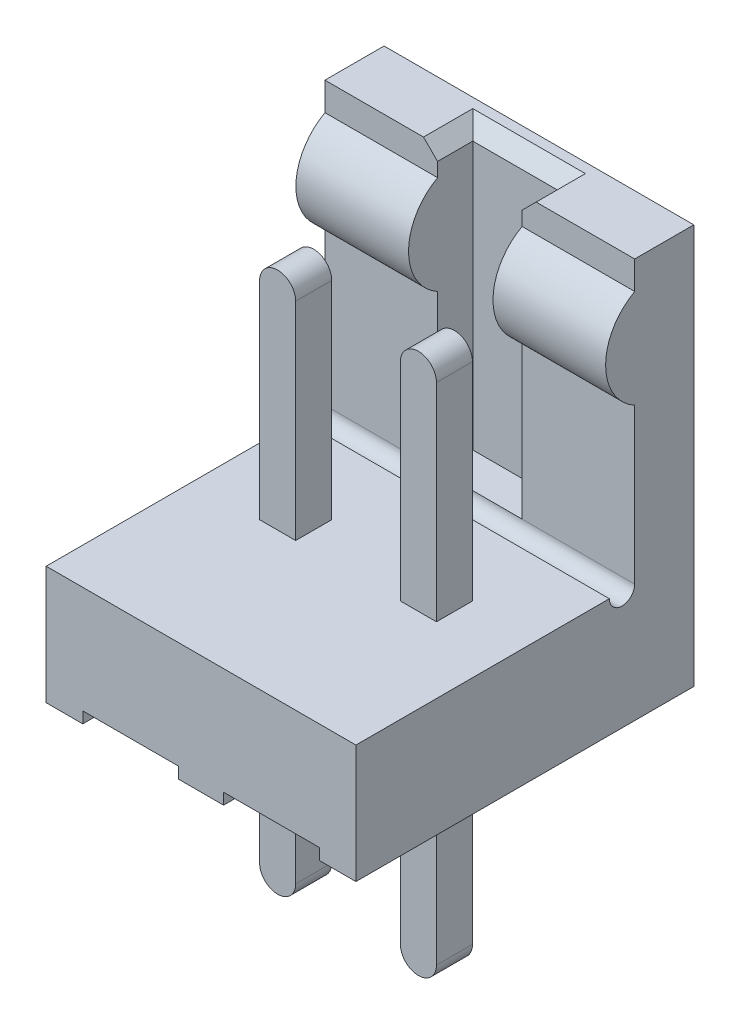
SolidWorks part; units mm, degrees
ref_plane "Front Plane" through (0, 0, 0) normal (0, 0, 1) x (1, 0, 0)
ref_plane "Top Plane" through (0, 0, 0) normal (0, 1, 0) x (1, 0, 0)
ref_plane "Right Plane" through (0, 0, 0) normal (1, 0, 0) x (0, 0, -1)
sketch "Sketch1" plane through (0, 0, 0) normal (1, 0, 0) x (0, 0, -1)
  line L0 (-3, 0) -> (3, 0)
  line L1 (3, 0) -> (3, 7.1)
  line L2 (3, 7.1) -> (1.95, 7.1)
  line L3 (1.95, 7.1) -> (1.95, 6.6)
  line L4 (-3, 0) -> (-3, 2.1)
  line L5 (-3, 2.1) -> (1.5, 2.1)
  line L6 (1.95, 2.1) -> (1.95, 4.85)
  arc A1 (1.95, 4.85) -> (1.95, 6.6) centre (2.4341, 5.725) cw
  arc A2 (1.95, 2.1) -> (1.5, 2.1) centre (1.725, 2.1) cw
  point P12 (0, 0)
  point P13 (1.95, 4.8078)
  dimension "D6" = 0.5
  dimension "D8" = 1
  dimension "D1" = 6
  dimension "D2" = 2.1
  dimension "D3" = 7.1
  dimension "D4" = 1.05
  dimension "D5" = 4.5
  dimension "D7" = 2.75
extrude "Boss-Extrude1" add sketch "Sketch1" along normal blind 2.75 and the other way blind 2.75
sketch "Sketch2" plane through (0, 2.1, 0) normal (0, 1, 0) x (1, 0, 0)
  line L0 (-2.75, 1.95) -> (2.75, 1.95)
  line L1 (-2.75, 1.95) -> (2.75, 1.95) construction
  line L3 (-0.75, 1.325) -> (0.75, 1.325)
  line L4 (-0.75, 1.325) -> (-0.75, 2.575)
  line L5 (-0.75, 2.575) -> (0.75, 2.575)
  line L6 (0.75, 1.325) -> (0.75, 2.575)
  line L7 (-0.75, 1.325) -> (0.75, 2.575) construction
  line L8 (-0.75, 2.575) -> (0.75, 1.325) construction
  point P2 (0, 1.95)
  dimension "D1" = 1.5
  dimension "D2" = 1.25
extrude "Cut-Extrude1" cut sketch "Sketch2" along normal through all
chamfer "Chamfer1" distance 0.25 angle 45 3 edges at (0.75, 7.1, -2.2625) (0, 7.1, -2.575) (-0.75, 7.1, -2.2625)
sketch "Sketch3" plane through (0, 0, 3) normal (0, 0, 1) x (1, 0, 0)
  line L1 (-2.75, 0) -> (2.75, 0) construction
  line L2 (-2.1, 0) -> (-0.4, 0)
  line L24 (-2.1, 0) -> (-2.1, 0.2)
  line L25 (-2.1, 0.2) -> (-0.4, 0.2)
  line L26 (-0.4, 0) -> (-0.4, 0.2)
  line L27 (-2.1, 0) -> (-2.75, 0) construction
  line L32 (0.4, 0) -> (2.1, 0)
  line L33 (0.4, 0) -> (0.4, 0.2)
  line L34 (0.4, 0.2) -> (2.1, 0.2)
  line L35 (2.1, 0) -> (2.1, 0.2)
  line L37 (-0.4, 0) -> (0.4, 0) construction
  line L38 (2.1, 0) -> (2.75, 0) construction
  point P6 (-1.1993, 0)
  point P19 (-1.2616, 0)
  dimension "D1" = 0.65
  dimension "D2" = 0.8
  dimension "D3" = 0.2
extrude "Cut-Extrude2" cut sketch "Sketch3" against normal through all
sketch "Sketch4" plane through (0, 2.1, 0) normal (0, 1, 0) x (1, 0, 0)
  line L0 (-2.75, 1.5) -> (-2.75, -3) construction
  line L1 (-1.57, -0.39) -> (-0.93, -0.39)
  line L2 (-1.57, -0.39) -> (-1.57, 0.25)
  line L3 (-1.57, 0.25) -> (-0.93, 0.25)
  line L4 (-0.93, -0.39) -> (-0.93, 0.25)
  line L5 (-1.57, -0.39) -> (-0.93, 0.25) construction
  line L6 (-1.57, 0.25) -> (-0.93, -0.39) construction
  line L11 (-2.75, 3) -> (2.75, 3) construction
  point P0 (-1.25, -0.07)
  dimension "D1" = 1.5
  dimension "D2" = 3.07
  dimension "D3" = 0.64
extrude "Boss-Extrude2" add sketch "Sketch4" along normal blind 4 and the other way blind 5.6 separate body
fillet "Fillet1" 2 edges at (-0.93, 6.1, 0.07) (-1.57, 6.1, 0.07) type full round first side face at (-0.93, 1.3, 0.07) second side face at (-1.57, 1.3, 0.07) middle face at (-1.25, 6.1, 0.07)
fillet "Fillet2" 2 edges at (-0.93, -3.5, 0.07) (-1.57, -3.5, 0.07) type full round first side face at (-0.93, 1.14, 0.07) second side face at (-1.57, 1.14, 0.07) middle face at (-1.25, -3.5, 0.07)
mirror "Mirror1" about plane through (0, 0, 0) normal (1, 0, 0) of bodies 104
